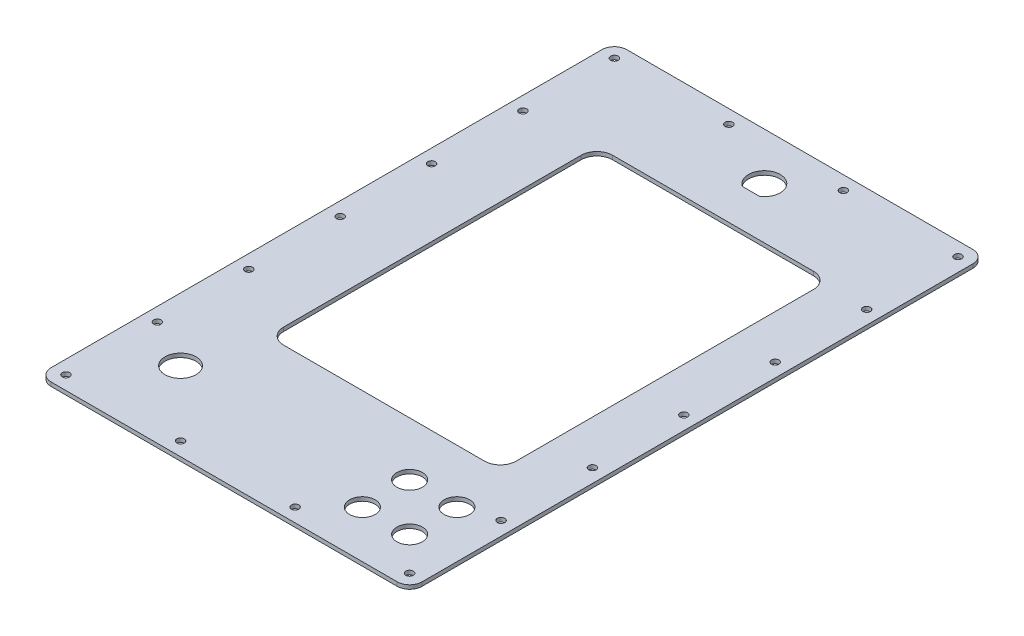
SolidWorks part; units mm, degrees
material "5052-H32"
ref_plane "Front Plane" through (0, 0, 0) normal (0, 0, 1) x (1, 0, 0)
ref_plane "Top Plane" through (0, 0, 0) normal (0, 1, 0) x (1, 0, 0)
ref_plane "Right Plane" through (0, 0, 0) normal (1, 0, 0) x (0, 0, -1)
sketch "Sketch9" plane through (0, 0, 0) normal (0, 1, 0) x (1, 0, 0)
  line L0 (-149.5, 0) -> (-149.5, 464)
  line L13 (-149.5, 464) -> (149.5, 464)
  line L14 (103.1625, 119.4438) -> (-84.1625, 119.4438)
  line L19 (149.5, 464) -> (149.5, 0)
  line L20 (103.1625, 119.4438) -> (103.1625, 384.5563)
  line L21 (103.1625, 384.5563) -> (-84.1625, 384.5563)
  line L22 (-84.1625, 119.4438) -> (-84.1625, 384.5563)
  line L23 (103.1625, 252) -> (-84.1625, 252) construction
  line L24 (9.5, 384.5562) -> (9.5, 119.4438) construction
  line L25 (-149.5, 0) -> (149.5, 0)
  line L26 (9.5, 464) -> (9.5, 425.9) construction
  line L27 (16.3702, 415.1) -> (2.6298, 415.1)
  arc A0 (16.3702, 415.1) -> (2.6298, 415.1) centre (9.5, 425.9) ccw
  circle A1 centre (-98.7, 63.5) radius 12.5
  circle A2 centre (111.4, 76.2) radius 10.287
  circle A3 centre (111.4, 38.1) radius 10.287
  circle A4 centre (73.3, 76.2) radius 10.287
  circle A5 centre (73.3, 38.1) radius 10.287
  point P8 (0, 0)
  point P17 (9.5, 438.7)
  point P19 (0, 0)
  dimension "D8" = 25.6
  dimension "D10" = 25
  dimension "D11" = 20.574
  dimension "D3" = 265.1125
  dimension "D4" = 187.325
  dimension "D1" = 299
  dimension "D2" = 464
  dimension "D6" = 140
  dimension "D5" = 212
  dimension "D7" = 23.6
  dimension "D9" = 38.1
  dimension "D12" = 38.1
  dimension "D13" = 38.1
  dimension "D15" = 38.1
  dimension "D16" = 63.5
  dimension "D17" = 50.8
  dimension "D14" = 38.1
extrude "Boss-Extrude7" add sketch "Sketch9" along normal blind 3.175 separate body contours L0 L25 L19 L13 L14 L22 L21 L20 region at (-143.9801, 0, -232)
fillet "Fillet4" radius 10 4 edges at (-149.5, 1.5875, -464) (149.5, 1.5875, -464) (-149.5, 1.5875, 0) (149.5, 1.5875, 0)
fillet "Fillet5" radius 12.7 4 edges at (-84.1625, 1.5875, -119.4438) (103.1625, 1.5875, -119.4438) (103.1625, 1.5875, -384.5563) (-84.1625, 1.5875, -384.5563)
sketch "Sketch10" plane through (0, 3.175, 0) normal (0, 1, 0) x (1, 0, 0)
  line L0 (-149.5, 10) -> (-149.5, 454) construction
  line L1 (-139.5, 0) -> (139.5, 0) construction
  circle A0 centre (-138.5, 11) radius 3
  circle A1 centre (-46.1667, 11) radius 3
  circle A2 centre (46.1667, 11) radius 3
  circle A3 centre (138.5, 11) radius 3
  circle A56 centre (-138.5, 84.6667) radius 3
  circle A57 centre (-138.5, 158.3333) radius 3
  circle A58 centre (-138.5, 232) radius 3
  circle A59 centre (-138.5, 305.6667) radius 3
  circle A60 centre (-138.5, 379.3333) radius 3
  circle A61 centre (-138.5, 453) radius 3
  circle A68 centre (138.5, 84.6667) radius 3
  circle A72 centre (138.5, 158.3333) radius 3
  circle A76 centre (138.5, 232) radius 3
  circle A80 centre (138.5, 305.6667) radius 3
  circle A84 centre (138.5, 379.3333) radius 3
  circle A86 centre (-46.1667, 453) radius 3
  circle A87 centre (46.1667, 453) radius 3
  circle A88 centre (138.5, 453) radius 3
  circle A102 centre (-46.1667, 84.6667) radius 3 [skipped]
  circle A103 centre (46.1667, 84.6667) radius 3 [skipped]
  circle A104 centre (-46.1667, 158.3333) radius 3 [skipped]
  circle A105 centre (46.1667, 158.3333) radius 3 [skipped]
  circle A106 centre (-46.1667, 232) radius 3 [skipped]
  circle A107 centre (46.1667, 232) radius 3 [skipped]
  circle A108 centre (-46.1667, 305.6667) radius 3 [skipped]
  circle A109 centre (46.1667, 305.6667) radius 3 [skipped]
  circle A110 centre (-46.1667, 379.3333) radius 3 [skipped]
  circle A111 centre (46.1667, 379.3333) radius 3 [skipped]
  dimension "D1" = 6
  dimension "D2" = 11
  dimension "D3" = 11
  dimension "D6" = 73.6667
  dimension "D7" = 92.3333
  dimension "D4" = 4
  dimension "D5" = 7
extrude "Cut-Extrude1" cut sketch "Sketch10" against normal up to surface (3.175 mm away) up to face at (73.3, 0, -27.813)
equation "\"W\"= 255mm"
equation "\"L\"= 420mm"
equation "\"Offset\"= 18mm"
equation "\"H\"= 110mm"
equation "\"T\"= 4.7625 * 2 / 3mm"
equation "\"Inside Fillet Radius\"= 5.55625mm"
equation "\"Hole\"=25mm"
equation "\"D1@Sketch9\"=\"W\"+44"
equation "\"D2@Sketch9\"=\"L\"+44"
equation "\"D6@Sketch10\"=(\"L\"+22)/6"
equation "\"D7@Sketch10\"=(\"W\"+22)/3"
equation "\"D5@Sketch9\"=(\"L\"/2+20)-\"Offset\""
equation "\"Compartment Width1\"= 90mm"
equation "\"Compartment Width2\"= 90mm"
